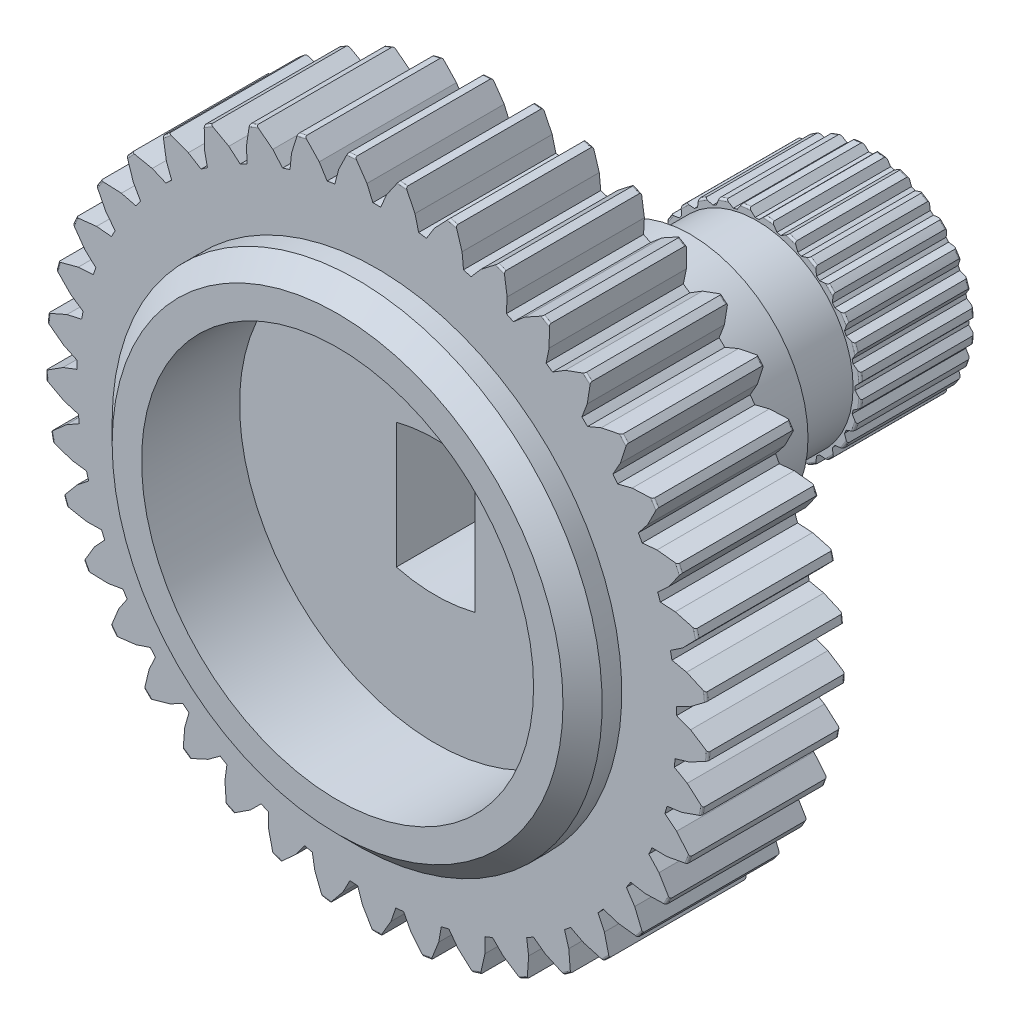
SolidWorks part; units mm, degrees
material "Latón de decoletaje, UNS C36000"
ref_plane "Alzado" through (0, 0, 0) normal (0, 0, 1) x (1, 0, 0)
ref_plane "Planta" through (0, 0, 0) normal (0, 1, 0) x (1, 0, 0)
ref_plane "Vista lateral" through (0, 0, 0) normal (1, 0, 0) x (0, 0, -1)
sketch "Croquis1" plane through (0, 0, 0) normal (0, 0, 1) x (1, 0, 0)
  circle A0 centre (0, 0) radius 8.45
  dimension "D1" = 16.9
extrude "Saliente-Extruir1" add sketch "Croquis1" along normal blind 3.5
fillet "Redondeo1" radius 0.05 2 edges at (8.45, 0, 0) (8.45, 0, 3.5)
sketch "Croquis2" plane through (0, 0, 3.5) normal (0, 0, 1) x (1, 0, 0)
  circle A0 centre (0, 0) radius 6.25
  dimension "D1" = 12.5
extrude "Saliente-Extruir2" add sketch "Croquis2" along normal blind 1
chamfer "Chaflán1" distance 0.5 angle 45 1 edges at (6.25, 0, 4.5)
sketch "Croquis3" plane through (0, 0, 0) normal (0, 0, -1) x (-1, 0, 0)
  line L0 (0, 0) -> (0, 11.5897) construction
  line L1 (0.55, 8.6) -> (-0.55, 8.6)
  line L2 (-0.55, 8.6) -> (-0.55, 8.4321)
  line L3 (-0.55, 8.4321) -> (-0.25, 8)
  line L4 (-0.25, 8) -> (-0.1, 7.6493)
  line L5 (0.25, 8) -> (0.1, 7.6493)
  line L6 (0.55, 8.6) -> (0.55, 8.4321)
  line L7 (0.55, 8.4321) -> (0.25, 8)
  circle A0 centre (0, 0) radius 7.65
  circle A1 centre (0, 0) radius 8.45 construction
  circle A2 centre (0, 0) radius 3.5
  point P16 (0, 8.6)
  circle M6 centre (0, 0) radius 8.4
  dimension "D1" = 15.3
  dimension "D7" = 7
  dimension "D2" = 0.55
  dimension "D3" = 0.1
  dimension "D4" = 8.6
  dimension "D5" = 8
  dimension "D6" = 0.25
extrude "Cortar-Extruir1" cut sketch "Croquis3" against normal blind 3.8 contours L0 A0 L5 L7 M6 | A0 L0 L3 L4 M6 | L0 L1 L2 L3 M6 | L0 L7 L6 L1 M6 region at (0.1687, 8.1144, 0) region at (-0.1687, 8.1144, 0) region at (0.2771, 8.4977, 0) region at (-0.2771, 8.4977, 0)
pattern_circular "MatrizC1" count 41 over 360 about axis through (0, 0, 3.5) along (0, 0, -1) of "Cortar-Extruir1"
extrude "Saliente-Extruir3" add sketch "Croquis3<3>" along normal blind 1.8 contours A2 region at (0, 0, 0)
sketch "Croquis3<3>" plane through (0, 0, 0) normal (0, 0, -1) x (-1, 0, 0) same geometry as "Croquis3"
sketch "Croquis5" plane through (0, 0, -1.8) normal (0, 0, -1) x (-1, 0, 0)
  circle A0 centre (0, 0) radius 3
  dimension "D1" = 6
extrude "Saliente-Extruir4" add sketch "Croquis5" along normal blind 2.7
sketch "Croquis6" plane through (0, 0, -4.5) normal (0, 0, -1) x (-1, 0, 0)
  circle A0 centre (0, 0) radius 2.65
  dimension "D1" = 5.3
extrude "Saliente-Extruir5" add sketch "Croquis6" along normal blind 4.6
sketch "Croquis8" plane through (0, 0, -4.5) normal (0, 0, -1) x (-1, 0, 0)
  circle A0 centre (0, 0) radius 2.45
  dimension "D1" = 4.9
extrude "Cortar-Extruir3" cut sketch "Croquis8" along normal blind 1.7 flip side to cut
fillet "Redondeo4" radius 0.05 2 edges at (-2.65, 0, -9.1) (-2.65, 0, -6.2)
sketch "Croquis7" plane through (0, 0, -9.1) normal (0, 0, -1) x (-1, 0, 0)
  line L0 (0, 0) -> (0, 4.6002) construction
  line L1 (0.2, 2.7) -> (-0.2, 2.7)
  line L2 (-0.2, 2.7) -> (-0.2, 2.6424)
  line L3 (-0.2, 2.6424) -> (-0.12, 2.5662)
  line L4 (-0.12, 2.5662) -> (-0.05, 2.4995)
  line L5 (0.2, 2.7) -> (0.2, 2.6424)
  line L6 (0.2, 2.6424) -> (0.12, 2.5662)
  line L7 (0.12, 2.5662) -> (0.05, 2.4995)
  circle A0 centre (0, 0) radius 2.5
  circle A2 centre (0, 0) radius 2.65 construction
  point P12 (0, 2.7)
  dimension "D1" = 5
  dimension "D3" = 0.05
  dimension "D2" = 0.2
  dimension "D4" = 0.12
  dimension "D5" = 2.7
extrude "Cortar-Extruir2" cut sketch "Croquis7" against normal blind 2.9 contours L0 A0 L7 L6 | L0 L1 L2 | L0 L5 L1 | A0 L0 L3 L4 region at (0.0818, 2.619, -9.1) region at (-0.0818, 2.619, -9.1)
pattern_circular "MatrizC2" count 28 over 360 about axis through (0, 0, -9.1) along (0, 0, 1) of "Cortar-Extruir2"
sketch "Croquis9" plane through (0, 0, 0) normal (0, 0, -1) x (-1, 0, 0)
  circle A0 centre (0, 6.3) radius 0.7
  circle A1 centre (0, 0) radius 3.5 construction
  point P2 (0, -3.5)
  point P3 (0, 7)
  dimension "D1" = 1.4
  dimension "D2" = 10.5
extrude "Cortar-Extruir4" cut sketch "Croquis9" against normal blind 1
sketch "Croquis10" plane through (0, 0, -9.1) normal (0, 0, -1) x (-1, 0, 0)
  circle A0 centre (0, 0) radius 1.5
  dimension "D1" = 3
extrude "Cortar-Extruir5" cut sketch "Croquis10" against normal blind 4
chamfer "Chaflán2" distance 0.3 angle 45 1 edges at (-1.5, 0, -9.1)
sketch "Croquis11" plane through (0, 0, 4.5) normal (0, 0, 1) x (1, 0, 0)
  circle A0 centre (0, 0) radius 5
  dimension "D1" = 10
extrude "Cortar-Extruir6" cut sketch "Croquis11" against normal blind 2.5
sketch "Croquis12" plane through (0, 0, 2) normal (0, 0, 1) x (1, 0, 0)
  line L0 (1, 1.6) -> (1, -1.6)
  line L1 (1, -1.6) -> (-1, -1.6) construction
  line L2 (-1, -1.6) -> (-1, 1.6)
  line L3 (-1, 1.6) -> (1, 1.6) construction
  arc A0 (-1, 1.6) -> (1, 1.6) centre (0, -2.273) cw
  arc A1 (1, -1.6) -> (-1, -1.6) centre (0, 2.273) cw
  point P3 (1, 0)
  point P5 (0, 1.6)
  dimension "D3" = 4
  dimension "D1" = 3.2
  dimension "D2" = 2
extrude "Cortar-Extruir7" cut sketch "Croquis12" against normal blind 3
